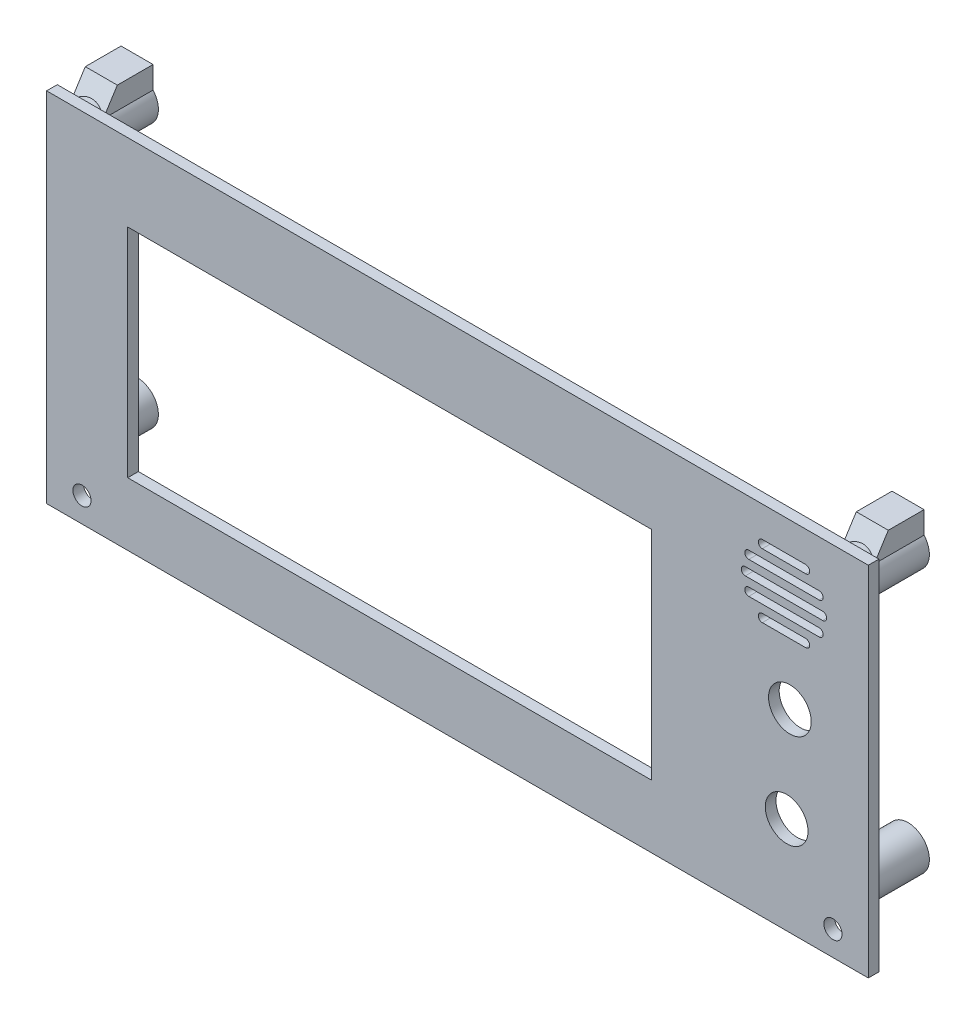
SolidWorks part; units mm, degrees
material "ABS"
ref_plane "Front Plane" through (0, 0, 0) normal (0, 0, 1) x (1, 0, 0)
ref_plane "Top Plane" through (0, 0, 0) normal (0, 1, 0) x (1, 0, 0)
ref_plane "Right Plane" through (0, 0, 0) normal (1, 0, 0) x (0, 0, -1)
ref_plane "Plane1" through (0, 0, -3.9) normal (0, 0, -1) x (-1, 0, 0)
sketch "Sketch1" plane through (0, 0, -3.9) normal (0, 0, -1) x (-1, 0, 0)
  line L0 (-57.1303, 15.75) -> (-65.2697, 15.75)
  line L1 (-65.2697, 14.25) -> (-57.1303, 14.25)
  line L2 (-65.2697, 27.75) -> (-57.1303, 27.75)
  line L3 (-57.1303, 26.25) -> (-65.2697, 26.25)
  line L4 (-68.45, 21.75) -> (-53.95, 21.75)
  line L5 (-53.95, 20.25) -> (-68.45, 20.25)
  line L6 (-54.5998, 18.75) -> (-67.8002, 18.75)
  line L7 (-67.8002, 17.25) -> (-54.5998, 17.25)
  line L8 (-54.5998, 23.25) -> (-67.8002, 23.25)
  line L9 (-67.8002, 24.75) -> (-54.5998, 24.75)
  line L10 (-36.4, 19) -> (61.8, 19)
  line L11 (61.8, 19) -> (61.8, -21.7)
  line L12 (61.8, -21.7) -> (-36.4, -21.7)
  line L13 (-36.4, -21.7) -> (-36.4, 19)
  line L14 (77, -33.5) -> (77, 33.5)
  line L15 (77, 33.5) -> (-77, 33.5)
  line L16 (-77, 33.5) -> (-77, -33.5)
  line L17 (-77, -33.5) -> (77, -33.5)
  line L18 (77, 33.5) -> (-77, -33.5) construction
  line L19 (-77, 33.5) -> (77, -33.5) construction
  line L20 (-53.2, 21) -> (-69.2, 21) construction
  line L21 (60.1, 18.5) -> (-34.7, 18.5) construction
  line L22 (-35.9, 17.3) -> (-35.9, -20) construction
  line L23 (61.3, -20) -> (61.3, 17.3) construction
  line L24 (-34.7, -21.2) -> (60.1, -21.2) construction
  line L25 (-75, 31.5) -> (75, 31.5) construction
  line L26 (75, 31.5) -> (75, -23.5) construction
  line L27 (58.4859, -31.5) -> (-33.0859, -31.5) construction
  line L28 (-75, -23.5) -> (-75, 31.5) construction
  arc A0 (-65.2697, 15.75) -> (-65.2697, 14.25) centre (-65.2697, 15) ccw
  arc A1 (-57.1303, 14.25) -> (-57.1303, 15.75) centre (-57.1303, 15) ccw
  arc A2 (-57.1303, 27.75) -> (-57.1303, 26.25) centre (-57.1303, 27) cw
  arc A3 (-65.2697, 26.25) -> (-65.2697, 27.75) centre (-65.2697, 27) cw
  arc A4 (-53.95, 21.75) -> (-53.95, 20.25) centre (-53.95, 21) cw
  arc A5 (-68.45, 20.25) -> (-68.45, 21.75) centre (-68.45, 21) cw
  circle A6 centre (-61.7, -15.35) radius 4
  circle A7 centre (-62.3, 2.75) radius 4
  arc A8 (-67.8002, 18.75) -> (-67.8002, 17.25) centre (-67.8002, 18) ccw
  arc A9 (-54.5998, 17.25) -> (-54.5998, 18.75) centre (-54.5998, 18) ccw
  arc A10 (-67.8002, 23.25) -> (-67.8002, 24.75) centre (-67.8002, 24) cw
  arc A11 (-54.5998, 24.75) -> (-54.5998, 23.25) centre (-54.5998, 24) cw
  circle A12 centre (-61.2, 21) radius 8 construction
  circle A13 centre (-61.7, -15.35) radius 1.65 construction
  circle A14 centre (-62.3, 2.75) radius 3 construction
  circle A15 centre (-61.2, 21) radius 6 construction
  dimension "D8" = 2
  dimension "D9" = 2
  dimension "D16" = 16
  dimension "D17" = 8
  dimension "D18" = 8
  dimension "D2" = 2
  dimension "D3" = 0.5
  dimension "D4" = 0.5
  dimension "D5" = 0.5
  dimension "D6" = 0.5
  dimension "D7" = 2
  dimension "D11" = 1.5
  dimension "D12" = 1.5
  dimension "D13" = 1.5
  dimension "D14" = 1.5
  dimension "D15" = 1.5
extrude "Boss-Extrude1" add sketch "Sketch1" against normal blind 2
sketch "Sketch2" plane through (0, 0, -3.9) normal (0, 0, -1) x (-1, 0, 0)
  line L1 (72.25, 28.75) -> (-72.25, 28.75) construction
  line L2 (72.25, 28.75) -> (72.25, -20.75) construction
  line L3 (72.25, -20.75) -> (-72.25, -20.75) construction
  line L4 (-72.25, 28.75) -> (-72.25, -20.75) construction
  circle A0 centre (-72.25, 28.75) radius 4
  circle A1 centre (-72.25, 28.75) radius 1.3
  circle A2 centre (-72.25, -20.75) radius 4
  circle A3 centre (-72.25, -20.75) radius 1.3
  circle A4 centre (72.25, -20.75) radius 4
  circle A5 centre (72.25, -20.75) radius 1.3
  circle A6 centre (72.25, 28.75) radius 4
  circle A7 centre (72.25, 28.75) radius 1.3
  circle A8 centre (-72.25, 28.75) radius 1.5 construction
  circle A9 centre (72.25, -20.75) radius 1.5 construction
  dimension "D1" = 8
  dimension "D2" = 2.6
extrude "Boss-Extrude2" add sketch "Sketch2" along normal blind 10.2
ref_axis "Axis1" through (-72.25, 28.75, -14.1) along (0, 0, 1)
ref_axis "Axis2" through (72.25, 28.75, -14.1) along (0, 0, 1)
ref_plane "Plane2" through (72.25, 0, 0) normal (1, 0, 0) x (0, 0, -1)
ref_plane "Plane3" through (-72.25, 0, 0) normal (-1, 0, 0) x (0, 0, 1)
sketch "Sketch3" plane through (-72.25, 0, 0) normal (-1, 0, 0) x (0, 0, 1)
  line L0 (-7.4, 35.55) -> (-3.9, 30.05)
  line L2 (-7.4, 35.55) -> (-14.1, 35.55)
  line L3 (-3.9, 30.05) -> (-14.1, 30.05) construction
  line L4 (-3.9, 30.05) -> (-14.1, 30.05)
  line L5 (-14.1, 30.05) -> (-14.1, 35.55)
  line L6 (-3.9, -33.5) -> (-3.9, 33.5) construction
  line L7 (-14.1, 32.75) -> (-14.1, 24.75) construction
  dimension "D1" = 3.5
  dimension "D2" = 5.5
extrude "Boss-Extrude3" add sketch "Sketch3" along normal mid plane 6
sketch "Sketch5" plane through (72.25, 0, 0) normal (1, 0, 0) x (0, 0, -1)
  line L0 (4.7564, 31.3958) -> (7.4, 35.55) construction
  line L1 (7.4, 35.55) -> (14.1, 35.55) construction
  line L2 (14.1, 35.55) -> (14.1, 31.3958) construction
  line L3 (3.9, 30.05) -> (7.4, 35.55)
  line L4 (7.4, 35.55) -> (14.1, 35.55)
  line L5 (14.1, 35.55) -> (14.1, 30.05)
  line L6 (14.1, 30.05) -> (3.9, 30.05)
  line L10 (14.1, 30.05) -> (3.9, 30.05) construction
extrude "Boss-Extrude4" add sketch "Sketch5" along normal mid plane 6
sketch "Sketch4" plane through (0, 0, -1.9) normal (0, 0, 1) x (1, 0, 0)
  circle A0 centre (-70.3766, -28.8766) radius 1.7
  circle A1 centre (70.3766, -28.8766) radius 1.7
  dimension "D1" = 3.4
extrude "Cut-Extrude1" cut sketch "Sketch4" against normal up to surface (2 mm away) up to face at (-12.7, -1.35, -3.9)
